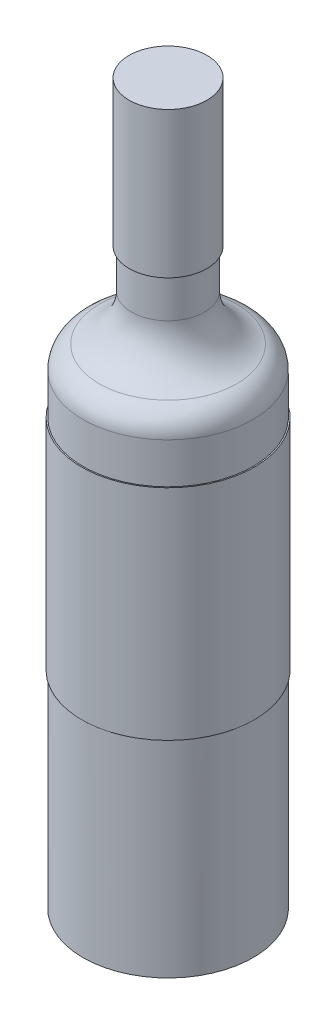
SolidWorks part; units mm, degrees
ref_plane "Front Plane" through (0, 0, 0) normal (0, 0, 1) x (1, 0, 0)
ref_plane "Top Plane" through (0, 0, 0) normal (0, 1, 0) x (1, 0, 0)
ref_plane "Right Plane" through (0, 0, 0) normal (1, 0, 0) x (0, 0, -1)
sketch "Sketch2" plane through (0, 0, 0) normal (0, 1, 0) x (1, 0, 0)
  circle A0 centre (0, 0) radius 35
  dimension "D1" = 70
extrude "Boss-Extrude1" add sketch "Sketch2" along normal blind 200
ref_axis "Axis1" through (0, 200, 0) along (0, -1, 0)
sketch "Sketch3" plane through (0, 200, 0) normal (0, 1, 0) x (1, 0, 0)
  circle A0 centre (0, 0) radius 15
  dimension "D1" = 30
extrude "Boss-Extrude2" add sketch "Sketch3" along normal blind 95
fillet "Fillet1" radius 20 1 edges at (0, 200, 15)
fillet "Fillet2" radius 10 1 edges at (0, 200, 35)
sketch "Sketch4" plane through (0, 295, 0) normal (0, 1, 0) x (1, 0, 0)
  circle A0 centre (0, 0) radius 16
  circle A1 centre (0, 0) radius 15 construction
  dimension "D1" = 1
extrude "Boss-Extrude3" add sketch "Sketch4" against normal blind 60 from offset 1
sketch "Sketch5" plane through (0, 0, 0) normal (0, -1, 0) x (1, 0, 0)
  circle A0 centre (0, 0) radius 35.5
  circle A1 centre (0, 0) radius 35 construction
  dimension "D1" = 0.5
extrude "Boss-Extrude4" add sketch "Sketch5" against normal blind 90 from offset 85 offset against normal yes
